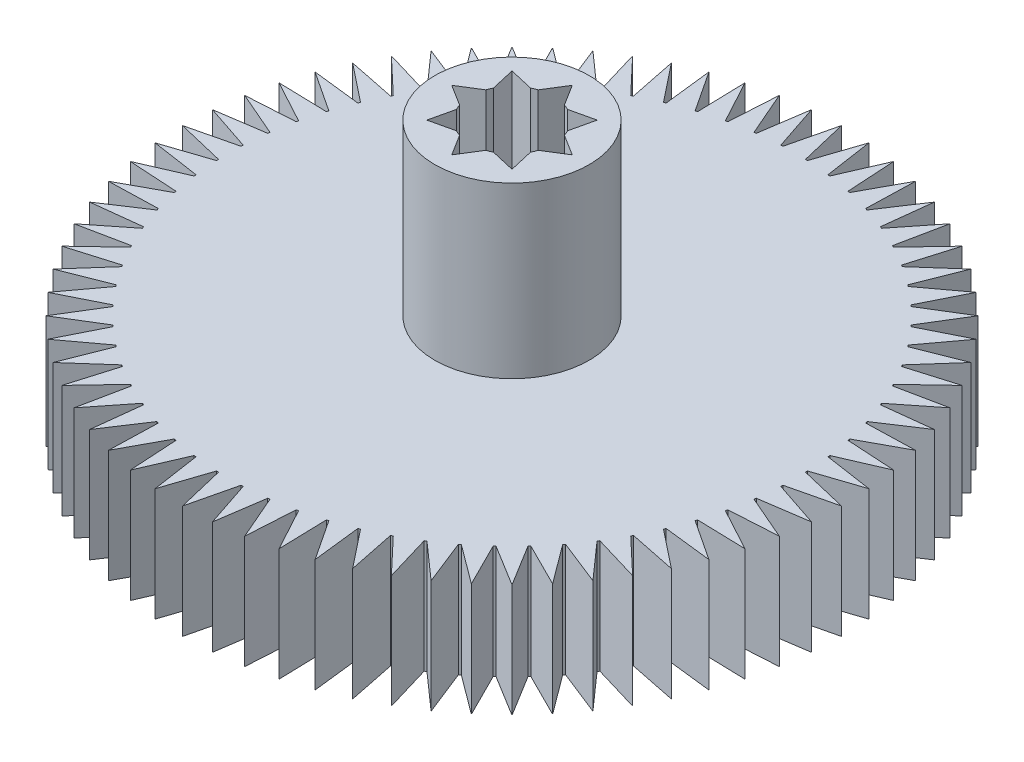
SolidWorks part; units mm, degrees
ref_plane "Спереди" through (0, 0, 0) normal (0, 0, 1) x (1, 0, 0)
ref_plane "Сверху" through (0, 0, 0) normal (0, 1, 0) x (1, 0, 0)
ref_plane "Справа" through (0, 0, 0) normal (1, 0, 0) x (0, 0, -1)
sketch "Эскиз1" plane through (0, 0, 0) normal (0, 1, 0) x (1, 0, 0)
  line L4 (0, 1.5) -> (2.2, 1.5)
  line L5 (0, 1.5) -> (-2.2, 1.5)
  line L6 (0, -1.5) -> (-2.2, -1.5)
  line L7 (0, -1.5) -> (2.2, -1.5)
  line L229 (-0.5999, 14.988) -> (0, 17.5)
  line L230 (0.5999, 14.988) -> (0, 17.5)
  line L233 (1.9039, 14.8787) -> (1.5252, 17.4334)
  line L234 (0.7087, 14.9832) -> (1.5252, 17.4334)
  line L235 (3.1934, 14.6561) -> (3.0388, 17.2341)
  line L236 (2.0119, 14.8645) -> (3.0388, 17.2341)
  line L237 (4.4586, 14.322) -> (4.5293, 16.9037)
  line L238 (3.2997, 14.6326) -> (4.5293, 16.9037)
  line L239 (5.6899, 13.8789) -> (5.9854, 16.4446)
  line L240 (4.5625, 14.2893) -> (5.9854, 16.4446)
  line L241 (6.8779, 13.3302) -> (7.3958, 15.8604)
  line L242 (5.7905, 13.8373) -> (7.3958, 15.8604)
  line L243 (8.0135, 12.68) -> (8.75, 15.1554)
  line L244 (6.9745, 13.2799) -> (8.75, 15.1554)
  line L245 (9.0882, 11.9334) -> (10.0376, 14.3352)
  line L246 (8.1054, 12.6215) -> (10.0376, 14.3352)
  line L247 (10.0936, 11.0959) -> (11.2488, 13.4058)
  line L248 (9.1746, 11.8671) -> (11.2488, 13.4058)
  line L249 (11.0223, 10.1739) -> (12.3744, 12.3744)
  line L250 (10.1739, 11.0223) -> (12.3744, 12.3744)
  line L251 (11.8671, 9.1746) -> (13.4058, 11.2488)
  line L252 (11.0959, 10.0936) -> (13.4058, 11.2488)
  line L253 (12.6215, 8.1054) -> (14.3352, 10.0376)
  line L254 (11.9334, 9.0882) -> (14.3352, 10.0376)
  line L255 (13.2799, 6.9745) -> (15.1554, 8.75)
  line L256 (12.68, 8.0135) -> (15.1554, 8.75)
  line L257 (13.8373, 5.7905) -> (15.8604, 7.3958)
  line L258 (13.3302, 6.8779) -> (15.8604, 7.3958)
  line L259 (14.2893, 4.5625) -> (16.4446, 5.9854)
  line L260 (13.8789, 5.6899) -> (16.4446, 5.9854)
  line L261 (14.6326, 3.2997) -> (16.9037, 4.5293)
  line L262 (14.322, 4.4586) -> (16.9037, 4.5293)
  line L263 (14.8645, 2.0119) -> (17.2341, 3.0388)
  line L264 (14.6561, 3.1934) -> (17.2341, 3.0388)
  line L265 (14.9832, 0.7087) -> (17.4334, 1.5252)
  line L266 (14.8787, 1.9039) -> (17.4334, 1.5252)
  line L267 (14.988, -0.5999) -> (17.5, 0)
  line L268 (14.988, 0.5999) -> (17.5, 0)
  line L269 (14.8787, -1.9039) -> (17.4334, -1.5252)
  line L270 (14.9832, -0.7087) -> (17.4334, -1.5252)
  line L271 (14.6561, -3.1934) -> (17.2341, -3.0388)
  line L272 (14.8645, -2.0119) -> (17.2341, -3.0388)
  line L273 (14.322, -4.4586) -> (16.9037, -4.5293)
  line L274 (14.6326, -3.2997) -> (16.9037, -4.5293)
  line L275 (13.8789, -5.6899) -> (16.4446, -5.9854)
  line L276 (14.2893, -4.5625) -> (16.4446, -5.9854)
  line L277 (13.3302, -6.8779) -> (15.8604, -7.3958)
  line L278 (13.8373, -5.7905) -> (15.8604, -7.3958)
  line L279 (12.68, -8.0135) -> (15.1554, -8.75)
  line L280 (13.2799, -6.9745) -> (15.1554, -8.75)
  line L281 (11.9334, -9.0882) -> (14.3352, -10.0376)
  line L282 (12.6215, -8.1054) -> (14.3352, -10.0376)
  line L283 (11.0959, -10.0936) -> (13.4058, -11.2488)
  line L284 (11.8671, -9.1746) -> (13.4058, -11.2488)
  line L285 (10.1739, -11.0223) -> (12.3744, -12.3744)
  line L286 (11.0223, -10.1739) -> (12.3744, -12.3744)
  line L287 (9.1746, -11.8671) -> (11.2488, -13.4058)
  line L288 (10.0936, -11.0959) -> (11.2488, -13.4058)
  line L289 (8.1054, -12.6215) -> (10.0376, -14.3352)
  line L290 (9.0882, -11.9334) -> (10.0376, -14.3352)
  line L291 (6.9745, -13.2799) -> (8.75, -15.1554)
  line L292 (8.0135, -12.68) -> (8.75, -15.1554)
  line L293 (5.7905, -13.8373) -> (7.3958, -15.8604)
  line L294 (6.8779, -13.3302) -> (7.3958, -15.8604)
  line L295 (4.5625, -14.2893) -> (5.9854, -16.4446)
  line L296 (5.6899, -13.8789) -> (5.9854, -16.4446)
  line L297 (3.2997, -14.6326) -> (4.5293, -16.9037)
  line L298 (4.4586, -14.322) -> (4.5293, -16.9037)
  line L299 (2.0119, -14.8645) -> (3.0388, -17.2341)
  line L300 (3.1934, -14.6561) -> (3.0388, -17.2341)
  line L301 (0.7087, -14.9832) -> (1.5252, -17.4334)
  line L302 (1.9039, -14.8787) -> (1.5252, -17.4334)
  line L303 (-0.5999, -14.988) -> (0, -17.5)
  line L304 (0.5999, -14.988) -> (0, -17.5)
  line L305 (-1.9039, -14.8787) -> (-1.5252, -17.4334)
  line L306 (-0.7087, -14.9832) -> (-1.5252, -17.4334)
  line L307 (-3.1934, -14.6561) -> (-3.0388, -17.2341)
  line L308 (-2.0119, -14.8645) -> (-3.0388, -17.2341)
  line L309 (-4.4586, -14.322) -> (-4.5293, -16.9037)
  line L310 (-3.2997, -14.6326) -> (-4.5293, -16.9037)
  line L311 (-5.6899, -13.8789) -> (-5.9854, -16.4446)
  line L312 (-4.5625, -14.2893) -> (-5.9854, -16.4446)
  line L313 (-6.8779, -13.3302) -> (-7.3958, -15.8604)
  line L314 (-5.7905, -13.8373) -> (-7.3958, -15.8604)
  line L315 (-8.0135, -12.68) -> (-8.75, -15.1554)
  line L316 (-6.9745, -13.2799) -> (-8.75, -15.1554)
  line L317 (-9.0882, -11.9334) -> (-10.0376, -14.3352)
  line L318 (-8.1054, -12.6215) -> (-10.0376, -14.3352)
  line L319 (-10.0936, -11.0959) -> (-11.2488, -13.4058)
  line L320 (-9.1746, -11.8671) -> (-11.2488, -13.4058)
  line L321 (-11.0223, -10.1739) -> (-12.3744, -12.3744)
  line L322 (-10.1739, -11.0223) -> (-12.3744, -12.3744)
  line L323 (-11.8671, -9.1746) -> (-13.4058, -11.2488)
  line L324 (-11.0959, -10.0936) -> (-13.4058, -11.2488)
  line L325 (-12.6215, -8.1054) -> (-14.3352, -10.0376)
  line L326 (-11.9334, -9.0882) -> (-14.3352, -10.0376)
  line L327 (-13.2799, -6.9745) -> (-15.1554, -8.75)
  line L328 (-12.68, -8.0135) -> (-15.1554, -8.75)
  line L329 (-13.8373, -5.7905) -> (-15.8604, -7.3958)
  line L330 (-13.3302, -6.8779) -> (-15.8604, -7.3958)
  line L331 (-14.2893, -4.5625) -> (-16.4446, -5.9854)
  line L332 (-13.8789, -5.6899) -> (-16.4446, -5.9854)
  line L333 (-14.6326, -3.2997) -> (-16.9037, -4.5293)
  line L334 (-14.322, -4.4586) -> (-16.9037, -4.5293)
  line L335 (-14.8645, -2.0119) -> (-17.2341, -3.0388)
  line L336 (-14.6561, -3.1934) -> (-17.2341, -3.0388)
  line L337 (-14.9832, -0.7087) -> (-17.4334, -1.5252)
  line L338 (-14.8787, -1.9039) -> (-17.4334, -1.5252)
  line L339 (-14.988, 0.5999) -> (-17.5, 0)
  line L340 (-14.988, -0.5999) -> (-17.5, 0)
  line L341 (-14.8787, 1.9039) -> (-17.4334, 1.5252)
  line L342 (-14.9832, 0.7087) -> (-17.4334, 1.5252)
  line L343 (-14.6561, 3.1934) -> (-17.2341, 3.0388)
  line L344 (-14.8645, 2.0119) -> (-17.2341, 3.0388)
  line L345 (-14.322, 4.4586) -> (-16.9037, 4.5293)
  line L346 (-14.6326, 3.2997) -> (-16.9037, 4.5293)
  line L347 (-13.8789, 5.6899) -> (-16.4446, 5.9854)
  line L348 (-14.2893, 4.5625) -> (-16.4446, 5.9854)
  line L349 (-13.3302, 6.8779) -> (-15.8604, 7.3958)
  line L350 (-13.8373, 5.7905) -> (-15.8604, 7.3958)
  line L351 (-12.68, 8.0135) -> (-15.1554, 8.75)
  line L352 (-13.2799, 6.9745) -> (-15.1554, 8.75)
  line L353 (-11.9334, 9.0882) -> (-14.3352, 10.0376)
  line L354 (-12.6215, 8.1054) -> (-14.3352, 10.0376)
  line L355 (-11.0959, 10.0936) -> (-13.4058, 11.2488)
  line L356 (-11.8671, 9.1746) -> (-13.4058, 11.2488)
  line L357 (-10.1739, 11.0223) -> (-12.3744, 12.3744)
  line L358 (-11.0223, 10.1739) -> (-12.3744, 12.3744)
  line L359 (-9.1746, 11.8671) -> (-11.2488, 13.4058)
  line L360 (-10.0936, 11.0959) -> (-11.2488, 13.4058)
  line L361 (-8.1054, 12.6215) -> (-10.0376, 14.3352)
  line L362 (-9.0882, 11.9334) -> (-10.0376, 14.3352)
  line L363 (-6.9745, 13.2799) -> (-8.75, 15.1554)
  line L364 (-8.0135, 12.68) -> (-8.75, 15.1554)
  line L365 (-5.7905, 13.8373) -> (-7.3958, 15.8604)
  line L366 (-6.8779, 13.3302) -> (-7.3958, 15.8604)
  line L367 (-4.5625, 14.2893) -> (-5.9854, 16.4446)
  line L368 (-5.6899, 13.8789) -> (-5.9854, 16.4446)
  line L369 (-3.2997, 14.6326) -> (-4.5293, 16.9037)
  line L370 (-4.4586, 14.322) -> (-4.5293, 16.9037)
  line L371 (-2.0119, 14.8645) -> (-3.0388, 17.2341)
  line L372 (-3.1934, 14.6561) -> (-3.0388, 17.2341)
  line L373 (-0.7087, 14.9832) -> (-1.5252, 17.4334)
  line L374 (-1.9039, 14.8787) -> (-1.5252, 17.4334)
  arc A0 (-2.2, 1.5) -> (-2.2, -1.5) centre (1.4803, 0) ccw
  arc A1 (2.2, 1.5) -> (2.2, -1.5) centre (-1.1791, 0) cw
  circle A3 centre (0, 0) radius 15
  point P158 (0, 0)
  point P224 (0, 0)
  point P231 (0, 0)
  point P233 (-0.2391, -0.2604)
  point P234 (0, 0)
  dimension "D1" = 72
extrude "Бобышка-Вытянуть5" add sketch "Эскиз1" along normal blind 6 contours A3 | A3 | A3 | A3 | A3 | A3 | A3 | A3 | A3 | A3 | A3 | A3 | A3 | A3 | A3 | A3 | A3 | A3 | A3 | A3 | A3 | A3 | A3 | A3 | A3 | A3 | A3 | A3 | A3 | A3 | A3 | A3 | A3 | A3 | A3 | A3 | A3 | A3 | A3 | A3 | A3 | A3 | A3 | A3 | A3 | A3 | A3 | A3 | A3 | A3 | A3 | A3 | A3 | A3 | A3 | A3 | A3 | A3 | A3 | A3 | A3 | A3 | A3 | A3 | A3 | A3 | A3 | A3 | A3 | A3 | A3 | A3 | A3 region at (0, 0, -15.8307) region at (0, 0, -14.5757) region at (-1.3797, 0, -15.7704) region at (1.3797, 0, -15.7704) region at (-2.749, 0, -15.5902) region at (2.749, 0, -15.5902) region at (-4.0973, 0, -15.2913) region at (4.0973, 0, -15.2913) region at (-5.4144, 0, -14.876) region at (5.4144, 0, -14.876) region at (-6.6903, 0, -14.3475) region at (6.6903, 0, -14.3475) region at (-7.9153, 0, -13.7098) region at (7.9153, 0, -13.7098) region at (-9.0801, 0, -12.9677) region at (9.0801, 0, -12.9677) region at (-10.1758, 0, -12.127) region at (10.1758, 0, -12.127) region at (-11.194, 0, -11.194) region at (11.194, 0, -11.194) region at (-12.127, 0, -10.1758) region at (12.127, 0, -10.1758) region at (-12.9677, 0, -9.0801) region at (12.9677, 0, -9.0801) region at (-13.7098, 0, -7.9153) region at (13.7098, 0, -7.9153) region at (-14.3475, 0, -6.6903) region at (14.3475, 0, -6.6903) region at (-14.876, 0, -5.4144) region at (14.876, 0, -5.4144) region at (-15.2913, 0, -4.0973) region at (15.2913, 0, -4.0973) region at (-15.5902, 0, -2.749) region at (15.5902, 0, -2.749) region at (-15.7704, 0, -1.3797) region at (15.7704, 0, -1.3797) region at (-15.8307, 0, 0) region at (15.8307, 0, 0) region at (-15.7704, 0, 1.3797) region at (15.7704, 0, 1.3797) region at (-15.5902, 0, 2.749) region at (15.5902, 0, 2.749) region at (-15.2913, 0, 4.0973) region at (15.2913, 0, 4.0973) region at (-14.876, 0, 5.4144) region at (14.876, 0, 5.4144) region at (-14.3475, 0, 6.6903) region at (14.3475, 0, 6.6903) region at (-13.7098, 0, 7.9153) region at (13.7098, 0, 7.9153) region at (-12.9677, 0, 9.0801) region at (12.9677, 0, 9.0801) region at (-12.127, 0, 10.1758) region at (12.127, 0, 10.1758) region at (-11.194, 0, 11.194) region at (11.194, 0, 11.194) region at (-10.1758, 0, 12.127) region at (10.1758, 0, 12.127) region at (-9.0801, 0, 12.9677) region at (9.0801, 0, 12.9677)
extrude "Бобышка-Вытянуть6" add sketch "Эскиз1<5>" along normal blind 6 contours L6 A0 L5 L4 A1 L7
sketch "Эскиз1<5>" plane through (0, 0, 0) normal (0, 1, 0) x (1, 0, 0) same geometry as "Эскиз1"
ref_plane "Плоскость3" through (0, 6, 0) normal (0, 1, 0) x (1, 0, 0)
ref_plane "Плоскость4" through (0, 15, 0) normal (0, -1, 0) x (-1, 0, 0)
sketch "Эскиз4" plane through (0, 6, 0) normal (0, 1, 0) x (1, 0, 0)
  circle A0 centre (0, 0) radius 4.1
ref_plane "Плоскость5" through (0, 0, 0) normal (0, -1, 0) x (-1, 0, 0)
extrude "Бобышка-Вытянуть10" add sketch "Эскиз4" along normal blind 9
ref_plane "Плоскость6" through (0, 15, 0) normal (0, 1, 0) x (1, 0, 0)
sketch "Эскиз7" plane through (0, 15, 0) normal (0, 1, 0) x (1, 0, 0)
  line L4 (-0.6949, 2.0874) -> (0, 3.2)
  line L5 (0.6949, 2.0874) -> (0, 3.2)
  line L9 (0.9846, 1.9674) -> (2.2627, 2.2627)
  line L10 (1.9674, 0.9846) -> (2.2627, 2.2627)
  line L11 (2.0874, 0.6949) -> (3.2, 0)
  line L12 (2.0874, -0.6949) -> (3.2, 0)
  line L13 (1.9674, -0.9846) -> (2.2627, -2.2627)
  line L14 (0.9846, -1.9674) -> (2.2627, -2.2627)
  line L15 (0.6949, -2.0874) -> (0, -3.2)
  line L16 (-0.6949, -2.0874) -> (0, -3.2)
  line L17 (-0.9846, -1.9674) -> (-2.2627, -2.2627)
  line L18 (-1.9674, -0.9846) -> (-2.2627, -2.2627)
  line L19 (-2.0874, -0.6949) -> (-3.2, 0)
  line L20 (-2.0874, 0.6949) -> (-3.2, 0)
  line L21 (-1.9674, 0.9846) -> (-2.2627, 2.2627)
  line L22 (-0.9846, 1.9674) -> (-2.2627, 2.2627)
  circle A0 centre (0, 0) radius 2.2
  point P23 (0, 0)
  point P30 (0, 0)
  point P31 (0, 0)
  dimension "D1" = 8
extrude "Вырез-Вытянуть1" cut sketch "Эскиз7" against normal blind 6 contours A0 | A0 | A0 L5 L4 | A0 | A0 | A0 | A0 | A0 | A0 region at (0, 15, -2.5094) region at (0, 15, 0) region at (-1.7744, 15, -1.7744) region at (1.7744, 15, -1.7744) region at (-2.5094, 15, 0) region at (2.5094, 15, 0) region at (-1.7744, 15, 1.7744) region at (1.7744, 15, 1.7744) region at (0, 15, 2.5094)
sketch "Эскиз9" plane through (0, 0, 0) normal (0, -1, 0) x (-1, 0, 0)
  line L0 (2.4818, 0.3015) -> (3.0311, 1.75)
  line L2 (1.502, 1.9985) -> (3.0311, 1.75)
  line L4 (-0.9798, 2.3) -> (0, 3.5)
  line L5 (0.9798, 2.3) -> (0, 3.5)
  line L6 (1.502, -1.9985) -> (3.0311, -1.75)
  line L7 (2.4818, -0.3015) -> (3.0311, -1.75)
  line L8 (-0.9798, -2.3) -> (0, -3.5)
  line L9 (0.9798, -2.3) -> (0, -3.5)
  line L10 (-2.4818, -0.3015) -> (-3.0311, -1.75)
  line L11 (-1.502, -1.9985) -> (-3.0311, -1.75)
  line L12 (-1.502, 1.9985) -> (-3.0311, 1.75)
  line L13 (-2.4818, 0.3015) -> (-3.0311, 1.75)
  circle A0 centre (0, 0) radius 2.5
  point P23 (0, 0)
  dimension "D1" = 6
extrude "Вырез-Вытянуть2" cut sketch "Эскиз9" against normal blind 4 contours A0 | A0 L6 L7 | A0 L0 L2 | A0 L8 L9 | A0 L12 L13 | A0 L5 L4 | A0 L10 L11 region at (-2.4182, 0, -1.3962) region at (0, 0, 0) region at (-2.4182, 0, 1.3962) region at (0, 0, -2.7923) region at (0, 0, 2.7923) region at (2.4182, 0, -1.3962) region at (2.4182, 0, 1.3962)
